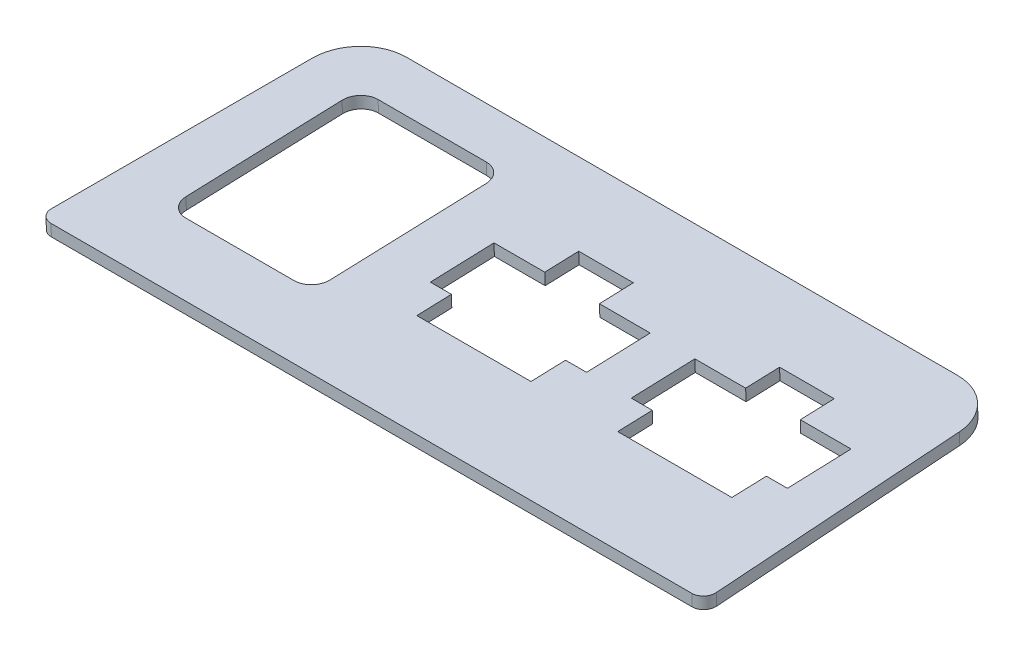
SolidWorks part; units mm, degrees
ref_plane "Front Plane" through (0, 0, 0) normal (0, 0, 1) x (1, 0, 0)
ref_plane "Top Plane" through (0, 0, 0) normal (0, 1, 0) x (1, 0, 0)
ref_plane "Right Plane" through (0, 0, 0) normal (1, 0, 0) x (0, 0, -1)
sketch "Sketch1" plane through (0, -69.2407, -2.4179) normal (0, 0.9994, 0.0349) x (1, 0, 0)
  line L4 (-46.8331, 44.5513) -> (46.8331, 44.5513) construction
  line L8 (-55.4003, -4.2069) -> (55.4003, -4.2069)
  line L9 (55.4003, -4.2069) -> (53.8625, 39.8305)
  line L10 (45.8674, 47.5513) -> (-45.8674, 47.5513)
  line L11 (-53.8625, 39.8305) -> (-55.4003, -4.2069)
  arc A4 (53.8625, 39.8305) -> (45.8674, 47.5513) centre (45.8674, 39.5513) ccw
  arc A5 (-45.8674, 47.5513) -> (-53.8625, 39.8305) centre (-45.8674, 39.5513) ccw
  dimension "D4" = 8
  dimension "D3" = 3
extrude "Boss-Extrude1" add sketch "Sketch1" along normal blind 2
sketch "Sketch2" plane through (0, -69.2407, -2.4179) normal (0, -0.9994, -0.0349) x (1, 0, 0)
  line L0 (-4.05, -28.7222) -> (-4.05, -34.3722)
  line L1 (-42.4354, -7.3722) -> (-24.4354, -7.3722)
  line L2 (-45.4354, -10.3722) -> (-45.4354, -36.3722)
  line L3 (-42.4354, -39.3722) -> (-24.4354, -39.3722)
  line L4 (-21.4354, -10.3722) -> (-21.4354, -36.3722)
  line L5 (-12.5, -18.1222) -> (-9, -18.1222)
  line L6 (-12.5, -18.1222) -> (-12.5, -28.7222)
  line L7 (-12.5, -28.7222) -> (-4.05, -28.7222)
  line L8 (13.5, -18.1222) -> (13.5, -28.7222)
  line L9 (-9, -12.3722) -> (10, -12.3722)
  line L10 (-9, -12.3722) -> (-9, -18.1222)
  line L11 (-4.05, -34.3722) -> (5.05, -34.3722)
  line L12 (10, -12.3722) -> (10, -18.1222)
  line L13 (10, -18.1222) -> (13.5, -18.1222)
  line L14 (5.05, -28.7222) -> (5.05, -34.3722)
  line L15 (5.05, -28.7222) -> (13.5, -28.7222)
  line L16 (-13, -9.8722) -> (14, -36.8722) construction
  line L17 (-13, -9.8722) -> (14, -9.8722) construction
  line L18 (-13, -9.8722) -> (-13, -36.8722) construction
  line L19 (-13, -36.8722) -> (14, -36.8722) construction
  line L20 (14, -9.8722) -> (14, -36.8722) construction
  line L21 (17.2177, 3.7502) -> (17.2177, -36.664) construction
  line L22 (46.9354, -23.4222) -> (20.9354, -23.4222) construction
  line L23 (33.9354, -12.3722) -> (33.9354, -34.3722) construction
  line L24 (20.4354, -9.8722) -> (20.4354, -36.8722) construction
  line L25 (47.4354, -36.8722) -> (20.4354, -36.8722) construction
  line L26 (47.4354, -9.8722) -> (47.4354, -36.8722) construction
  line L27 (47.4354, -9.8722) -> (20.4354, -9.8722) construction
  line L28 (-47.4354, -23.3722) -> (-45.4354, -23.3722) construction
  line L29 (-47.4354, -5.3722) -> (-19.4354, -5.3722) construction
  line L30 (-47.4354, -5.3722) -> (-47.4354, -41.3722) construction
  line L31 (-47.4354, -41.3722) -> (-19.4354, -41.3722) construction
  line L32 (-19.4354, -5.3722) -> (-19.4354, -41.3722) construction
  line L33 (-33.4354, -7.3722) -> (-33.4354, -5.3722) construction
  line L34 (0.5, -12.3722) -> (0.5, -34.3722) construction
  line L35 (-12.5, -23.4222) -> (13.5, -23.4222) construction
  line L36 (47.4354, -9.8722) -> (20.4354, -36.8722) construction
  line L37 (29.3854, -28.7222) -> (20.9354, -28.7222)
  line L38 (29.3854, -28.7222) -> (29.3854, -34.3722)
  line L39 (24.4354, -18.1222) -> (20.9354, -18.1222)
  line L40 (24.4354, -12.3722) -> (24.4354, -18.1222)
  line L41 (38.4854, -34.3722) -> (29.3854, -34.3722)
  line L42 (43.4354, -12.3722) -> (43.4354, -18.1222)
  line L43 (43.4354, -12.3722) -> (24.4354, -12.3722)
  line L44 (20.9354, -18.1222) -> (20.9354, -28.7222)
  line L45 (46.9354, -28.7222) -> (38.4854, -28.7222)
  line L46 (46.9354, -18.1222) -> (46.9354, -28.7222)
  line L47 (46.9354, -18.1222) -> (43.4354, -18.1222)
  line L48 (38.4854, -28.7222) -> (38.4854, -34.3722)
  line L49 (20.4354, -23.3722) -> (14, -23.3722) construction
  line L51 (47.4354, -23.3722) -> (51.4354, -23.3722) construction
  line L52 (55.4003, 4.2069) -> (53.8625, -39.8305) construction
  line L53 (-46.8331, -44.5513) -> (46.8331, -44.5513) construction
  line L54 (-13, -23.3722) -> (-19.4354, -23.3722) construction
  line L55 (-33.4354, -5.3722) -> (-33.4354, -2.1931) construction
  line L56 (-33.4354, -41.3722) -> (-33.4354, -44.5513) construction
  line L57 (-53.8625, -39.8305) -> (-55.4003, 4.2069) construction
  line L58 (-47.4354, -23.3722) -> (-51.4354, -23.3722) construction
  line L59 (48.0329, -2.1931) -> (-48.0329, -2.1931) construction
  arc A0 (-45.4354, -36.3722) -> (-42.4354, -39.3722) centre (-42.4354, -36.3722) ccw
  arc A1 (-24.4354, -39.3722) -> (-21.4354, -36.3722) centre (-24.4354, -36.3722) ccw
  arc A2 (-24.4354, -7.3722) -> (-21.4354, -10.3722) centre (-24.4354, -10.3722) cw
  arc A3 (-42.4354, -7.3722) -> (-45.4354, -10.3722) centre (-42.4354, -10.3722) ccw
  point P28 (0.5, -23.3722)
  point P63 (33.9354, -23.3722)
  dimension "D1" = 3
  dimension "D2" = 32
  dimension "D3" = 24
  dimension "D4" = 28
  dimension "D5" = 36
  dimension "D6" = 26
  dimension "D7" = 22
  dimension "D8" = 10.6
  dimension "D9" = 19
  dimension "D10" = 9.1
  dimension "D11" = 5.75
  dimension "D12" = 27
  dimension "D13" = 27
  dimension "D14" = 4
  dimension "D15" = 3
  dimension "D16" = 3
extrude "Cut-Extrude1" cut sketch "Sketch2" against normal up to next
fillet "Fillet1" radius 2 2 edges at (-55.4003, -68.3881, 1.8213) (55.4003, -68.3881, 1.8213)
